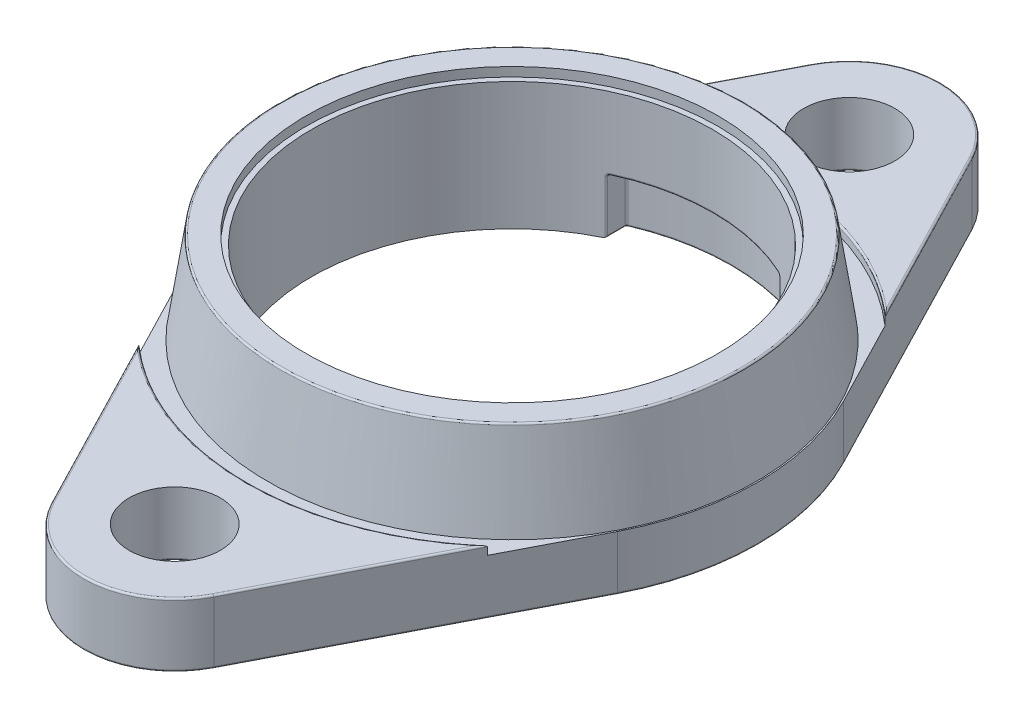
SolidWorks part; units mm, degrees
material "Zinco AC41A Liga, como fundido"
ref_plane "Plano frontal" through (0, 0, 0) normal (0, 0, 1) x (1, 0, 0)
ref_plane "Plano superior" through (0, 0, 0) normal (0, 1, 0) x (1, 0, 0)
ref_plane "Plano direito" through (0, 0, 0) normal (1, 0, 0) x (0, 0, -1)
sketch "Esboço3" plane through (0, 0, 0) normal (0, 1, 0) x (1, 0, 0)
  line L0 (-11.9907, 6.2027) -> (-4.441, 20.7973)
  line L1 (4.441, 20.7973) -> (11.9907, 6.2027)
  line L2 (-11.9907, -6.2027) -> (-4.441, -20.7973)
  line L3 (4.441, -20.7973) -> (11.9907, -6.2027)
  circle A0 centre (0, 0) radius 11
  arc A1 (-11.9907, 6.2027) -> (-11.9907, -6.2027) centre (0, 0) ccw
  arc A2 (-4.441, 20.7973) -> (4.441, 20.7973) centre (0, 18.5) cw
  arc A3 (-4.441, -20.7973) -> (4.441, -20.7973) centre (0, -18.5) ccw
  arc A4 (11.9907, -6.2027) -> (11.9907, 6.2027) centre (0, 0) ccw
  circle A5 centre (0, 18.5) radius 2.5
  circle A6 centre (0, -18.5) radius 2.5
  dimension "D1" = 22
  dimension "D2" = 27
  dimension "D4" = 47
  dimension "D3" = 5
  dimension "D5" = 5
  dimension "D6" = 5
extrude "Ressalto-extrusão1" add sketch "Esboço3" along normal blind 3
sketch "Esboço4" plane through (0, 0, 0) normal (1, 0, 0) x (0, 0, -1)
  line L0 (0, 0) -> (0, 3) construction
  line L1 (6.2027, 3) -> (-6.2027, 3) construction
  line L2 (-11, 3) -> (-11, 7.5)
  line L3 (-11, 7.5) -> (-11.3, 7.5)
  line L4 (-11.3, 7.5) -> (-11.3, 8)
  line L5 (-11.3, 8) -> (-12.675, 8)
  line L6 (-12.675, 8) -> (-13.425, 3)
  line L7 (-20.7973, 3) -> (-6.2027, 3) construction
  line L8 (-13.425, 3) -> (-11, 3)
  dimension "D1" = 4.5
  dimension "D2" = 12.675
  dimension "D3" = 13.425
  dimension "D4" = 0.5
  dimension "D5" = 0.3
revolve "Revolução1" add sketch "Esboço4" angle 360 about L0
sketch "Esboço6" plane through (0, 3, 0) normal (0, 1, 0) x (1, 0, 0)
  line L0 (-9.5595, 10.9026) -> (-4.441, 20.7973)
  line L1 (-4.441, 20.7973) -> (-11.9907, 6.2027) construction
  line L2 (4.441, 20.7973) -> (9.5595, 10.9026)
  line L3 (11.9907, 6.2027) -> (4.441, 20.7973) construction
  line L4 (-9.5595, -10.9026) -> (-4.441, -20.7973)
  line L5 (-11.9907, -6.2027) -> (-4.441, -20.7973) construction
  line L6 (4.441, -20.7973) -> (9.5595, -10.9026)
  line L7 (4.441, -20.7973) -> (11.9907, -6.2027) construction
  arc A0 (-4.441, 20.7973) -> (4.441, 20.7973) centre (0, 18.5) cw
  arc A1 (-4.441, -20.7973) -> (4.441, -20.7973) centre (0, -18.5) ccw
  arc A2 (-9.5595, -10.9026) -> (9.5595, -10.9026) centre (0, 0) ccw
  arc A3 (9.5595, 10.9026) -> (-9.5595, 10.9026) centre (0, 0) ccw
  dimension "D1" = 29
extrude "Ressalto-extrusão2" add sketch "Esboço6" along normal blind 0.5
sketch "Esboço7" plane through (0, 0, 0) normal (0, -1, 0) x (1, 0, 0)
  line L11 (-2.8866, -19.9932) -> (-10.4363, -5.3986)
  line L12 (-10.4363, 5.3986) -> (-2.8866, 19.9932)
  line L13 (-4.3167, -17.2287) -> (-10.4363, -5.3986)
  line L14 (-10.4363, 5.3986) -> (-4.3167, 17.2287)
  line L19 (10.4363, -5.3986) -> (2.8866, -19.9932)
  line L20 (2.8866, 19.9932) -> (10.4363, 5.3986)
  line L21 (10.4363, -5.3986) -> (4.3167, -17.2287)
  line L22 (4.3167, 17.2287) -> (10.4363, 5.3986)
  arc A5 (-10.4363, 5.3986) -> (-10.4363, -5.3986) centre (0, 0) ccw
  arc A6 (-10.4363, 5.3986) -> (-10.4363, -5.3986) centre (0, 0) ccw
  arc A8 (4.3167, -17.2287) -> (-4.3167, -17.2287) centre (0, -18.5) ccw
  arc A9 (10.4363, -5.3986) -> (10.4363, 5.3986) centre (0, 0) ccw
  arc A10 (10.4363, -5.3986) -> (10.4363, 5.3986) centre (0, 0) ccw
  arc A11 (-4.3167, 17.2287) -> (4.3167, 17.2287) centre (0, 18.5) ccw
  dimension "D3" = 9
  dimension "D1" = 1.75
  dimension "D2" = 1.75
extrude "Corte-extrusão1" cut sketch "Esboço7" against normal blind 0.5
sketch "Esboço8" plane through (0, 0.5, 0) normal (0, -1, 0) x (1, 0, 0)
  line L0 (-4.75, 11.0199) -> (-4.75, 9.9216)
  line L1 (4.75, 11.0199) -> (4.75, 9.9216)
  line L2 (0, 0) -> (0, -16) construction
  line L3 (-4.75, -9.9216) -> (-4.75, -11.0199)
  line L4 (4.75, -9.9216) -> (4.75, -11.0199)
  arc A0 (-4.75, -11.0199) -> (4.75, -11.0199) centre (0, 0) ccw
  circle A3 centre (0, 0) radius 11 construction
  circle A4 centre (0, -18.5) radius 2.5 construction
  arc A5 (-4.75, -9.9216) -> (4.75, -9.9216) centre (0, 0) ccw
  arc A6 (4.75, 9.9216) -> (-4.75, 9.9216) centre (0, 0) ccw
  arc A7 (4.75, 11.0199) -> (-4.75, 11.0199) centre (0, 0) ccw
  dimension "D1" = 1
  dimension "D2" = 9.5
extrude "Corte-extrusão2" cut sketch "Esboço8" against normal blind 3
fillet "Filete1" radius 0.1 48 edges at (4.75, 0.5, -10.4707) (4.75, 2, -9.9216) (4.75, 0.5, 10.4707) (-4.75, 2, -11.0199) (4.75, 2, -11.0199) (0, 0.5, -12) (-4.75, 3.5, -10.4707) (0, 3.5, -11) (4.75, 3.5, -10.4707) (0, 3.5, -12) (0, 0, 21) (-8.2158, 0, 13.5) (0, 0, 23.5) (8.2158, 0, 13.5) (13.5, 0, 0) (8.2158, 0, -13.5) (0, 0, -23.5) (-8.2158, 0, -13.5) (-13.5, 0, 0) (0, 0, -16) (0, 0, 14) (-7.3765, 0, 11.3137) (-11.75, 0, 0) (-7.3765, 0, -11.3137) (0, 0, -14) (7.3765, 0, -11.3137) (11.75, 0, 0) (7.3765, 0, 11.3137) (7.0002, 3.5, 15.85) (0, 3.5, 23.5) (-7.0002, 3.5, 15.85) (0, 3.5, 14.5) (-7.0002, 3.5, -15.85) (0, 3.5, -23.5) (7.0002, 3.5, -15.85) (0, 3.5, -14.5) (-4.75, 0.5, -10.4707) (-4.75, 2, -9.9216) (4.75, 2, 11.0199) (4.75, 3.5, 10.4707) (0, 0.5, 12) (-4.75, 0.5, 10.4707) (-4.75, 3.5, 10.4707) (0, 3.5, 12) (4.75, 2, 9.9216) (0, 3.5, 11) (-4.75, 2, 9.9216) (0, 8, -12.675)
hole_wizard "Furo de diâmetro Ø5.0 (5)1" positions "3DSketch1" profile "Esboço9" hole size "Ø5.0" standard "ISO"
sketch3d "3DSketch1"
  arc A2 (4.3522, 3.5, -20.7514) -> (-4.3522, 3.5, -20.7514) centre (0, 3.5, -18.5) ccw construction
  arc A3 (-4.3522, 3.5, 20.7514) -> (4.3522, 3.5, 20.7514) centre (0, 3.5, 18.5) ccw construction
  point P0 (0, 3.5, -18.5)
  point P2 (0, 3.5, 18.5)
  point P17 (0, 8.4, -18.5)
  point P23 (0, 8.4, 18.5)
sketch "Esboço9" plane through (0, 3.5, -18.5) normal (1, 0, 0) x (0, 0, 1)
  line L0 (0, 0) -> (0, 12.8522)
  line L1 (0, 12.8522) -> (2.5, 11.35)
  line L2 (2.5, 11.35) -> (2.5, 0)
  line L5 (2.5, 0) -> (0, 0)
  line L10 (0, 12.8522) -> (-2.5, 11.35) construction
  line L11 (0, -6.35) -> (0, 107.95) construction
  dimension "Hole Dia." = 5
  dimension "Hole Depth" = 11.35
  dimension "Drill Angle" = 118
